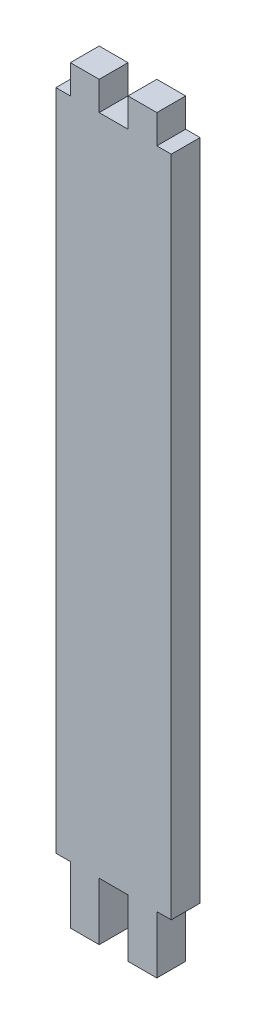
SolidWorks part; units mm, degrees
ref_plane "Front Plane" through (0, 0, 0) normal (0, 0, 1) x (1, 0, 0)
ref_plane "Top Plane" through (0, 0, 0) normal (0, 1, 0) x (1, 0, 0)
ref_plane "Right Plane" through (0, 0, 0) normal (1, 0, 0) x (0, 0, -1)
sketch "Sketch1" plane through (0, 0, 0) normal (0, 0, 1) x (1, 0, 0)
  line L0 (-7.5, 57.5) -> (-7.5, 62.5)
  line L1 (-10, -57.5) -> (-7.5, -57.5)
  line L2 (-10, -57.5) -> (-10, 57.5)
  line L3 (-10, 57.5) -> (-7.5, 57.5)
  line L4 (10, -57.5) -> (10, 57.5)
  line L5 (-10, -57.5) -> (10, 57.5) construction
  line L6 (-10, 57.5) -> (10, -57.5) construction
  line L7 (-7.5, 62.5) -> (-2.5, 62.5)
  line L8 (-2.5, 62.5) -> (-2.5, 57.5)
  line L9 (2.5, 57.5) -> (2.5, 62.5)
  line L10 (2.5, 62.5) -> (7.5, 62.5)
  line L11 (7.5, 62.5) -> (7.5, 57.5)
  line L12 (-2.5, 57.5) -> (2.5, 57.5)
  line L13 (7.5, 57.5) -> (10, 57.5)
  line L14 (-2.5, -57.5) -> (2.5, -57.5)
  line L16 (-7.5, -57.5) -> (-7.5, -62.4865)
  line L18 (-2.5, -57.5) -> (-2.5, -62.5)
  line L20 (2.5, -57.5) -> (2.5, -62.5)
  line L22 (7.5, -57.5) -> (7.5, -62.5)
  line L23 (7.5, -57.5) -> (10, -57.5)
  line L24 (-7.5, -62.4865) -> (-7.5, -67.4865)
  line L25 (-7.5, -67.4865) -> (-2.5, -67.4865)
  line L26 (-2.5, -67.4865) -> (-2.5, -62.5)
  line L27 (2.5, -62.5) -> (2.5, -67.4865)
  line L28 (2.5, -67.4865) -> (7.5, -67.4865)
  line L29 (7.5, -67.4865) -> (7.5, -62.5)
  point P0 (0, 0)
  dimension "D1" = 5
  dimension "D2" = 5
  dimension "D3" = 20
  dimension "D4" = 5
  dimension "D5" = 115
  dimension "D6" = 5
extrude "Boss-Extrude1" add sketch "Sketch1" along normal blind 5
